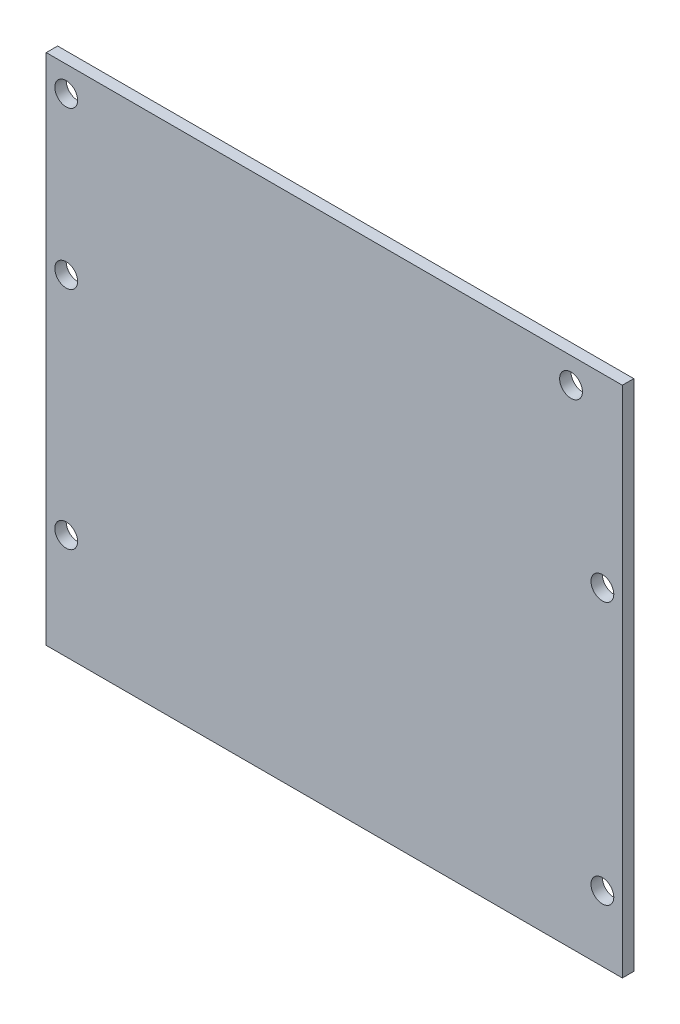
SolidWorks part; units mm, degrees
ref_plane "Plan de face" through (0, 0, 0) normal (0, 0, 1) x (1, 0, 0)
ref_plane "Plan de dessus" through (0, 0, 0) normal (0, 1, 0) x (1, 0, 0)
ref_plane "Plan de droite" through (0, 0, 0) normal (1, 0, 0) x (0, 0, -1)
sketch "Esquisse1" plane through (0, 0, 0) normal (0, 0, 1) x (1, 0, 0)
  line L1 (0, 0) -> (101, 0)
  line L2 (0, 0) -> (0, 90)
  line L3 (0, 90) -> (101, 90)
  line L4 (101, 0) -> (101, 90)
  dimension "D1" = 90
  dimension "D2" = 101
extrude "Boss.-Extru.1" add sketch "Esquisse1" along normal blind 2
sketch "Hole Sketch" plane through (0, 0, 2) normal (0, 0, 1) x (1, 0, 0)
  line L0 (0, 0) -> (101, 0) construction
  line L1 (101, 0) -> (101, 90) construction
  line L2 (0, 90) -> (0, 0) construction
  circle A0 centre (97.5, 11.5) radius 2
  circle A1 centre (97.5, 57.5) radius 2
  circle A2 centre (3.5, 18.5) radius 2
  circle A3 centre (3.5, 58) radius 2
  circle A4 centre (3.5, 85.5) radius 2
  circle A5 centre (92, 85.5) radius 2
  point P16 (0, 0)
  dimension "D1" = 4
  dimension "D2" = 11.5
  dimension "D3" = 3.5
  dimension "D4" = 57.5
  dimension "D5" = 3.5
  dimension "D6" = 18.5
  dimension "D7" = 58
  dimension "D8" = 85.5
  dimension "D9" = 9
extrude "Enlèv. mat.-Extru.1" cut sketch "Hole Sketch" against normal through all
